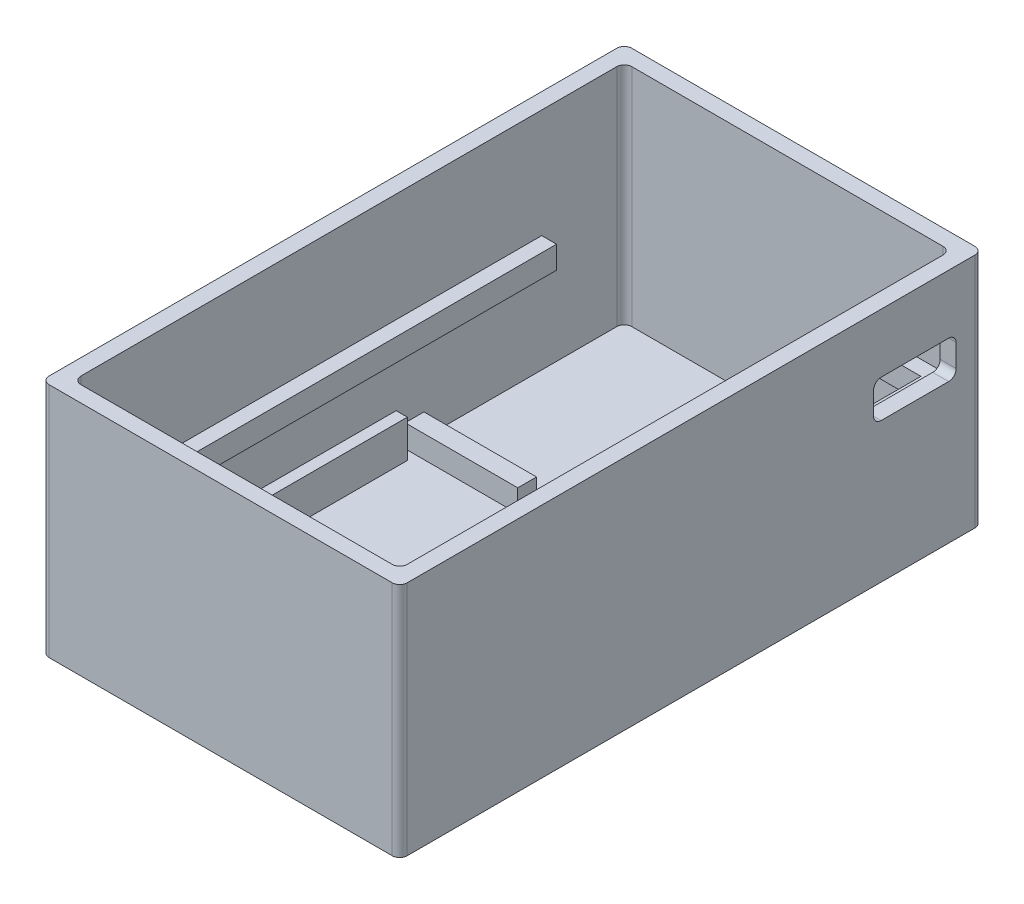
SolidWorks part; units mm, degrees
ref_plane "Front Plane" through (0, 0, 0) normal (0, 0, 1) x (1, 0, 0)
ref_plane "Top Plane" through (0, 0, 0) normal (0, 1, 0) x (1, 0, 0)
ref_plane "Right Plane" through (0, 0, 0) normal (1, 0, 0) x (0, 0, -1)
sketch "PCB Dimensions" plane through (0, 0, 0) normal (0, 1, 0) x (1, 0, 0)
  line L0 (0, 0) -> (-3.5355, 3.5355)
  line L1 (0, 0) -> (40.6457, 0)
  line L2 (0, 0) -> (0, -70.5657)
  line L3 (0, -70.5657) -> (40.6457, -70.5657)
  line L4 (40.6457, 0) -> (40.6457, -70.5657)
  line L5 (40.6457, -70.5657) -> (44.1812, -74.1012)
  line L6 (40.6457, 0) -> (44.1812, 3.5355)
  line L11 (0, -70.5657) -> (-3.5355, -74.1012)
  line L12 (44.1812, -74.1012) -> (-3.5355, -74.1012)
  line L13 (44.1812, -74.1012) -> (44.1812, 3.5355)
  line L14 (44.1812, 3.5355) -> (-3.5355, 3.5355)
  line L15 (-3.5355, -74.1012) -> (-3.5355, 3.5355)
extrude "Boss-Extrude3" add sketch "PCB Dimensions" along normal blind 1.5 contours L14 L15 L12 L13
sketch "Sketch5" plane through (0, 1.5, 0) normal (0, 1, 0) x (1, 0, 0)
  line L0 (-3.5355, 3.5355) -> (-1.4142, 1.4142)
  line L1 (-3.5355, 3.5355) -> (44.1812, 3.5355)
  line L2 (-3.5355, 3.5355) -> (-3.5355, -74.1012)
  line L7 (-3.5355, -74.1012) -> (44.1812, -74.1012)
  line L8 (44.1812, 3.5355) -> (44.1812, -74.1012)
  line L9 (44.1812, -74.1012) -> (42.0599, -71.9799)
  line L11 (-1.4142, 1.4142) -> (42.0599, 1.4142)
  line L12 (-1.4142, 1.4142) -> (-1.4142, -71.9799)
  line L13 (-1.4142, -71.9799) -> (42.0599, -71.9799)
  line L14 (42.0599, 1.4142) -> (42.0599, -71.9799)
extrude "Boss-Extrude5" add sketch "Sketch5" along normal blind 30 contours L14 L13 | L2 L7 L8 L1 region at (20.3228, 1.5, 35.2828)
fillet "Fillet1" radius 1 8 edges at (42.0599, 16.5, 71.9799) (-3.5355, 15.75, 74.1012) (44.1812, 15.75, 74.1012) (44.1812, 15.75, -3.5355) (-3.5355, 15.75, -3.5355) (-1.4142, 16.5, 71.9799) (42.0599, 16.5, -1.4142) (-1.4142, 16.5, -1.4142)
sketch "Sketch9" plane through (0, 1.5, 0) normal (0, 1, 0) x (1, 0, 0)
  line L3 (0.0799, -70.9799) -> (-1.8581, -70.9799)
  line L9 (0.0799, -28.9799) -> (-1.8581, -28.9799)
  line L10 (-1.8581, -70.9799) -> (-1.8581, -28.9799)
  line L15 (42.5038, -70.9799) -> (42.5038, -28.9799)
  line L16 (40.5658, -28.9799) -> (42.5038, -28.9799)
  line L18 (40.5658, -70.9799) -> (42.5038, -70.9799)
  line L21 (0.0799, -28.9799) -> (0.0799, -70.9799)
  line L23 (40.5658, -28.9799) -> (40.5658, -70.9799)
sketch "Sketch7" plane through (0, 1.5, 0) normal (0, 1, 0) x (1, 0, 0)
  line L3 (-0.4992, 0.4992) -> (41.1449, 0.4992)
  line L4 (-0.4992, 0.4992) -> (-0.4992, -71.0649)
  line L5 (-0.4992, -71.0649) -> (41.1449, -71.0649)
  line L6 (41.1449, 0.4992) -> (41.1449, -71.0649)
extrude "Boss-Extrude6" add sketch "Sketch9" along normal blind 5 contours L21 L3 L10 L9 | L23 L18 L15 L16
sketch "Sketch14" plane through (0, 1.5, 0) normal (0, 1, 0) x (1, 0, 0)
  line L2 (-1.4142, -27.7799) -> (13.5858, -27.7799)
  line L3 (-1.4142, -27.7799) -> (-1.4142, -25.2799)
  line L4 (-1.4142, -25.2799) -> (13.5858, -25.2799)
  line L5 (13.5858, -27.7799) -> (13.5858, -25.2799)
  line L6 (27.0599, -27.7799) -> (27.0599, -25.2799)
  line L7 (42.0599, -25.2799) -> (27.0599, -25.2799)
  line L8 (42.0599, -27.7799) -> (42.0599, -25.2799)
  line L9 (42.0599, -27.7799) -> (27.0599, -27.7799)
extrude "Boss-Extrude7" add sketch "Sketch14" along normal blind 3
sketch "Sketch15" plane through (44.1812, 0, 0) normal (1, 0, 0) x (0, 0, -1)
  line L1 (-73.1012, 31.5) -> (-73.1012, 0) construction
  line L3 (2.5355, 0) -> (2.5355, 31.5) construction
  line L4 (-73.1012, 14) -> (2.5355, 14)
  line L5 (-73.1012, 14) -> (-73.1012, 17)
  line L6 (-73.1012, 17) -> (2.5355, 17)
  line L7 (2.5355, 14) -> (2.5355, 17)
  line M8 (-73.1012, 31.5) -> (-73.1012, 0)
  line M10 (2.5355, 0) -> (2.5355, 31.5)
extrude "Boss-Extrude8" add sketch "Sketch15" against normal blind 46 contours L6 L4 M8 M10 region at (44.1812, 15.5, 35.2828)
sketch "Sketch17" plane through (0, 17, 0) normal (0, 1, 0) x (1, 0, 0)
  line L3 (40.0842, -63.5437) -> (0.5614, -63.5437)
  line L4 (40.0842, -63.5437) -> (40.0842, -0.5614)
  line L5 (40.0842, -0.5614) -> (0.5614, -0.5614)
  line L6 (0.5614, -63.5437) -> (0.5614, -0.5614)
extrude "Cut-Extrude1" cut sketch "Sketch17" against normal blind 3 contours L5 L6 L3 L4
sketch "Sketch18" plane through (0, 17, 0) normal (0, 1, 0) x (1, 0, 0)
  line L0 (-1.4142, -70.9799) -> (-1.4142, 0.4142) construction
  line L1 (-1.4142, -9.5858) -> (28.5858, -9.5858)
  line L4 (28.5858, -9.5858) -> (28.5858, 1.4142)
  line L5 (-0.4142, 1.4142) -> (41.0599, 1.4142) construction
  line L6 (-0.4142, 1.4142) -> (28.5858, 1.4142)
  line L7 (-1.4142, 0.4142) -> (-1.4142, -9.5858)
  arc A0 (-1.4142, 0.4142) -> (-0.4142, 1.4142) centre (-0.4142, 0.4142) cw
extrude "Cut-Extrude2" cut sketch "Sketch18" against normal blind 3
sketch "Sketch19" plane through (44.1812, 0, 0) normal (1, 0, 0) x (0, 0, -1)
  line L0 (2.5355, 0) -> (2.5355, 17)
  line L1 (2.5355, 0) -> (2.5355, 31.5) construction
  line L2 (0.0355, 23.65) -> (0.0355, 18.65)
  line L11 (0.0355, 18.65) -> (-10.9645, 18.65)
  line L13 (0.0355, 23.65) -> (-10.9645, 23.65)
  line L14 (-10.9645, 18.65) -> (-10.9645, 23.65)
extrude "Cut-Extrude3" cut sketch "Sketch19" against normal blind 10 contours L13 L14 L11 L2
fillet "Fillet2" radius 1 4 edges at (43.1205, 18.65, 10.9645) (43.1205, 18.65, -0.0355) (43.1205, 23.65, -0.0355) (43.1205, 23.65, 10.9645)
scale "Scale1" bodies to scale 113 scale about centroid uniform scaling yes scale factor 0.99
